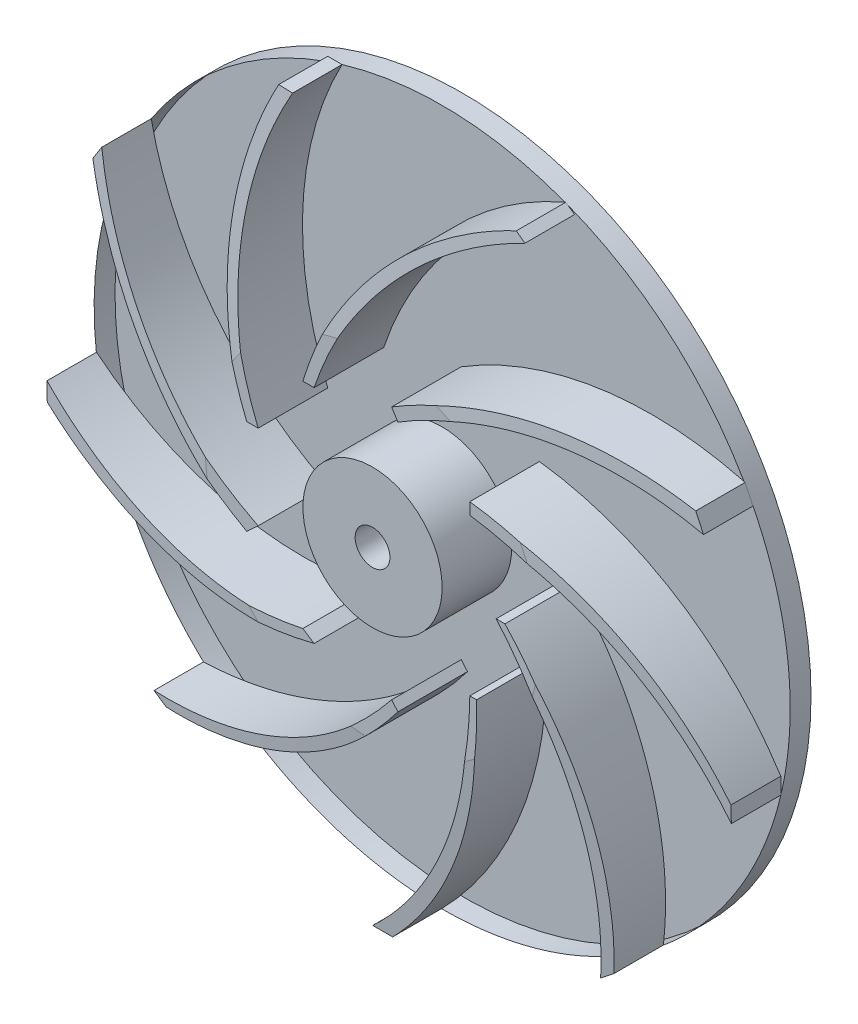
SolidWorks part; units mm, degrees
ref_plane "Front Plane" through (0, 0, 0) normal (0, 0, 1) x (1, 0, 0)
ref_plane "Top Plane" through (0, 0, 0) normal (0, 1, 0) x (1, 0, 0)
ref_plane "Right Plane" through (0, 0, 0) normal (1, 0, 0) x (0, 0, -1)
sketch "Sketch1" plane through (0, 0, 0) normal (0, 0, 1) x (1, 0, 0)
  circle A0 centre (0, 0) radius 50
  circle A1 centre (0, 0) radius 2.5
extrude "Boss-Extrude1" add sketch "Sketch1" along normal blind 3
sketch "Sketch2" plane through (0, 0, 3) normal (0, 0, 1) x (1, 0, 0)
  circle A0 centre (0, 0) radius 10
  circle A1 centre (0, 0) radius 2.5
extrude "Boss-Extrude2" add sketch "Sketch2" along normal blind 10
sketch "Sketch3" plane through (0, 0, 3) normal (0, 0, 1) x (1, 0, 0)
  line L0 (17.7683, 0) -> (19.0317, 0)
  line L1 (29.8886, -40.0833) -> (31.7807, -38.6003)
  line L2 (13.9769, 10.9855) -> (13.9769, 12.6691)
  line L3 (48.661, -11.4936) -> (48.661, -9.1413)
  line L4 (3.6456, 17.3996) -> (2.7447, 18.8413)
  line L5 (44.6644, 22.4741) -> (43.5325, 24.8446)
  line L6 (-8.3916, 15.6722) -> (-10.0084, 15.6722)
  line L7 (19.0317, 45.9259) -> (17.7683, 46.823)
  line L8 (-16.4331, 6.6116) -> (-18.0785, 6.6116)
  line L9 (-14.3768, 47.8885) -> (-16.4331, 47.8885)
  line L10 (-16.4331, -5.5426) -> (-18.0785, -7.0437)
  line L11 (-41.7954, 27.4435) -> (-43.0662, 25.4357)
  line L12 (-10.0084, -15.1034) -> (-8.3916, -16.1504)
  line L13 (-49.6575, -5.5426) -> (-49.6575, -8.2227)
  line L14 (2.7447, -17.5971) -> (3.6456, -18.6438)
  line L15 (-34.2842, -36.3949) -> (-32.4952, -37.5322)
  line L16 (13.9769, -11.4936) -> (14.9447, -11.4936)
  line L17 (-2.8691, -49.9176) -> (0, -49.9176)
  arc A0 (17.7683, 0) -> (29.8886, -40.0833) centre (-20.7527, -33.522) cw
  arc A1 (19.0317, 0) -> (31.7807, -38.6003) centre (-16.4331, -33.1189) cw
  arc A2 (13.9769, 10.9855) -> (48.661, -11.4936) centre (7.1586, -37.5322) cw
  arc A3 (13.9769, 12.6691) -> (48.661, -9.1413) centre (8.083, -35.1872) cw
  arc A4 (3.6456, 17.3996) -> (44.6644, 22.4741) centre (29.6091, -24.1502) cw
  arc A5 (2.7447, 18.8413) -> (43.5325, 24.8446) centre (30.1107, -25.5275) cw
  arc A6 (-8.3916, 15.6722) -> (19.0317, 45.9259) centre (39.6465, -0.316) cw
  arc A7 (-10.0084, 15.6722) -> (17.7683, 46.823) centre (37.2281, 1.5115) cw
  arc A8 (-16.4331, 6.6116) -> (-14.3768, 47.8885) centre (28.5887, 25.0584) cw
  arc A9 (-18.0785, 6.6116) -> (-16.4331, 47.8885) centre (28.2578, 25.4357) cw
  arc A10 (-16.4331, -5.5426) -> (-41.7954, 27.4435) centre (5.0945, 37.2529) cw
  arc A11 (-18.0785, -7.0437) -> (-43.0662, 25.4357) centre (7.0999, 38.1787) cw
  arc A12 (-10.0084, -15.1034) -> (-49.6575, -5.5426) centre (-19.8832, 30.939) cw
  arc A13 (-8.3916, -16.1504) -> (-49.6575, -8.2227) centre (-20.612, 31.603) cw
  arc A14 (2.7447, -17.5971) -> (-34.2842, -36.3949) centre (-36.3241, 13.493) cw
  arc A15 (3.6456, -18.6438) -> (-32.4952, -37.5322) centre (-34.145, 9.6444) cw
  arc A16 (13.9769, -11.4936) -> (-2.8691, -49.9176) centre (-39.2256, -11.0732) cw
  arc A17 (14.9447, -11.4936) -> (0, -49.9176) centre (-37.4247, -13.2433) cw
extrude "Boss-Extrude3" add sketch "Sketch3" along normal blind 10
sketch "Sketch4" plane through (0, 0, 0) normal (0, 1, 0) x (1, 0, 0)
  line L0 (0, 0) -> (0, 20) construction
  line L1 (24, 13) -> (51, 10)
  line L2 (51, 10) -> (51, 20)
  line L3 (51, 20) -> (24, 20)
  line L4 (24, 20) -> (24, 13)
sketch "Sketch5" plane through (0, 0, 0) normal (0, 1, 0) x (1, 0, 0)
  line L0 (0, 0) -> (0, -20) construction
  line L1 (24, -13) -> (51, -10)
  line L2 (2.7447, -13) -> (43.5325, -13) construction
  line L3 (51, -10) -> (51, -20)
  line L4 (51, -20) -> (24, -20)
  line L5 (24, -20) -> (24, -13)
revolve "Cut-Revolve2" cut sketch "Sketch5" angle 360 about L0
equation "\"D2\" = 100.0mm"
equation "\"Z\" = 9.0"
equation "\"beta2b\" = 45.0deg"
equation "\"t\" = 1.7mm"
equation "\"b1\" = 10.0mm"
equation "\"b2\" = 6.5mm"
equation "\"d1\" = 48.0mm"
equation "\"d_h\" = 20.0mm"
equation "\"d_bore\" = 5.0mm"
equation "\"t_bp\" = 3.0mm"
equation "\"beta1_LE\" = 42.0deg"
equation "\"r1_LE\" = 18.4mm"
equation "\"R_blade\" = 49.8453mm"
